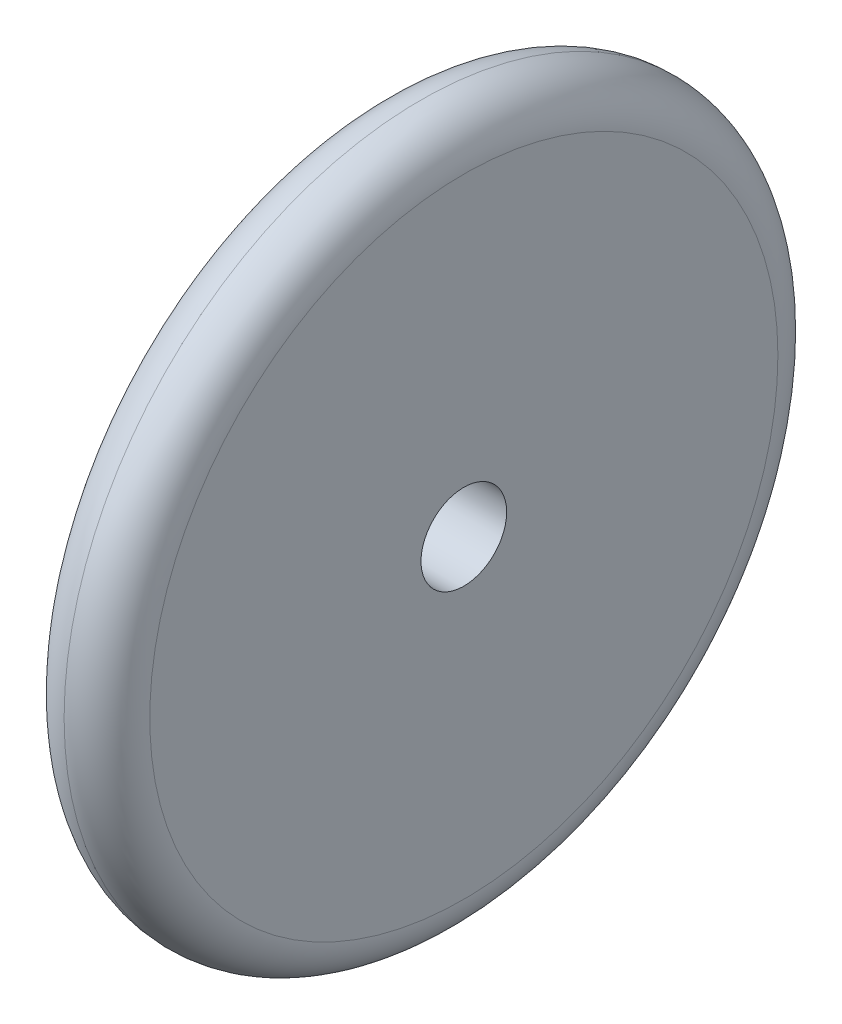
SolidWorks part; units mm, degrees
ref_plane "Front Plane" through (0, 0, 0) normal (0, 0, 1) x (1, 0, 0)
ref_plane "Top Plane" through (0, 0, 0) normal (0, 1, 0) x (1, 0, 0)
ref_plane "Right Plane" through (0, 0, 0) normal (1, 0, 0) x (0, 0, -1)
sketch "Sketch1" plane through (0, 0, 0) normal (1, 0, 0) x (0, 0, -1)
  circle A0 centre (0, 0) radius 125
  dimension "D1" = 250
extrude "Boss-Extrude1" add sketch "Sketch1" along normal blind 30
fillet "Fillet1" radius 15 2 edges at (0, 0, -125) (30, 0, -125)
sketch "Sketch2" plane through (30, 0, 0) normal (1, 0, 0) x (0, 0, -1)
  circle A0 centre (0, 0) radius 15
  dimension "D1" = 30
extrude "Cut-Extrude1" cut sketch "Sketch2" against normal through all
